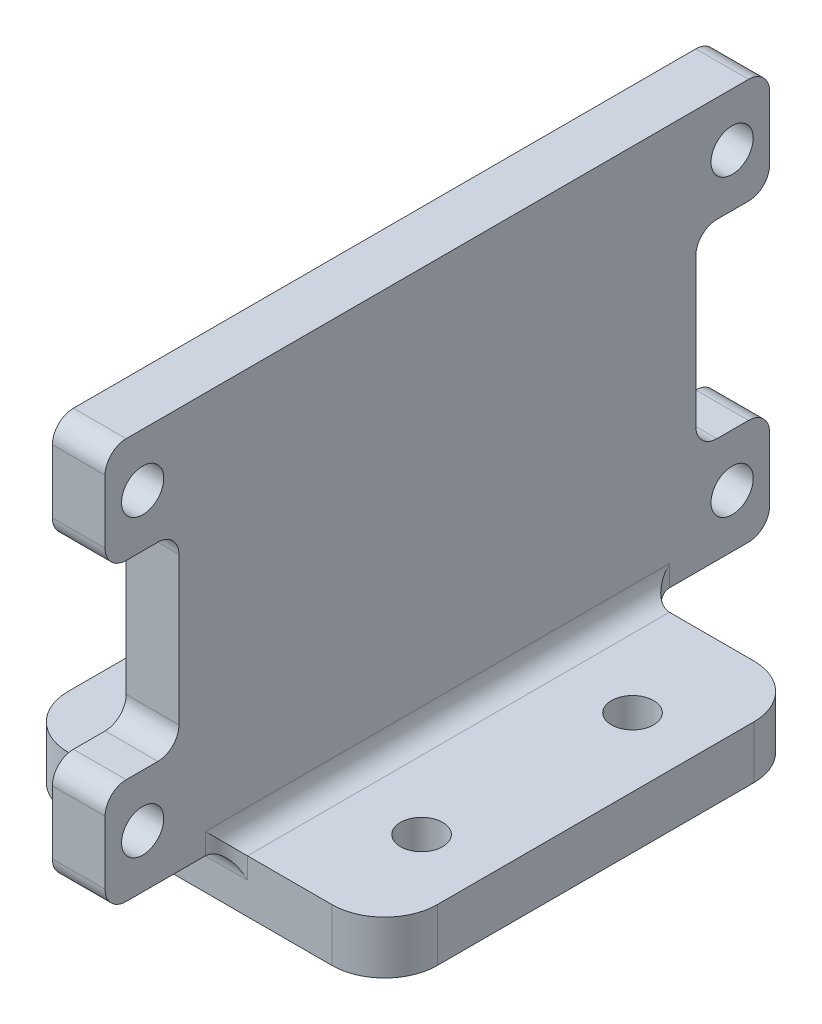
SolidWorks part; units mm, degrees
ref_plane "Plan de face" through (0, 0, 0) normal (0, 0, 1) x (1, 0, 0)
ref_plane "Plan de dessus" through (0, 0, 0) normal (0, 1, 0) x (1, 0, 0)
ref_plane "Plan de droite" through (0, 0, 0) normal (1, 0, 0) x (0, 0, -1)
sketch "Esquisse2" plane through (0, 0, 0) normal (0, 1, 0) x (1, 0, 0)
  line L1 (-17.5, -20) -> (17.5, -20)
  line L2 (-17.5, -20) -> (-17.5, 20)
  line L3 (-17.5, 20) -> (17.5, 20)
  line L4 (17.5, -20) -> (17.5, 20)
  line L5 (-17.5, -20) -> (17.5, 20) construction
  line L6 (-17.5, 20) -> (17.5, -20) construction
  point P0 (0, 0)
  dimension "D1" = 35
  dimension "D2" = 40
extrude "Boss.-Extru.1" add sketch "Esquisse2" along normal blind 5
sketch "Esquisse3" plane through (0, 0, 0) normal (1, 0, 0) x (0, 0, -1)
  line L1 (-31.5, 5) -> (31.5, 5)
  line L2 (-31.5, 5) -> (-31.5, 43)
  line L3 (-31.5, 43) -> (31.5, 43)
  line L4 (31.5, 5) -> (31.5, 43)
  line L5 (0, 5) -> (0, 0) construction
  line L6 (-20, 5) -> (20, 5) construction
  dimension "D1" = 38
  dimension "D2" = 63
extrude "Boss.-Extru.2" add sketch "Esquisse3" along normal mid plane 5
sketch "Esquisse4" plane through (2.5, 0, 0) normal (1, 0, 0) x (0, 0, -1)
  line L0 (-27.94, 37.97) -> (-27.94, 10.03) construction
  line L1 (-27.94, 10.03) -> (27.94, 10.03) construction
  line L2 (27.94, 10.03) -> (27.94, 37.97) construction
  line L3 (27.94, 37.97) -> (-27.94, 37.97) construction
  line L4 (0, 10.03) -> (0, 0) construction
  line L5 (-27.94, 24) -> (-31.5, 24) construction
  line L6 (-31.5, 43) -> (-31.5, 5) construction
  circle A0 centre (-27.94, 37.97) radius 2
  circle A1 centre (-27.94, 10.03) radius 2
  circle A2 centre (27.94, 37.97) radius 2
  circle A3 centre (27.94, 10.03) radius 2
  dimension "D1" = 4
  dimension "D2" = 4
  dimension "D3" = 4
  dimension "D4" = 55.88
  dimension "D5" = 27.94
extrude "Enlèv. mat.-Extru.1" cut sketch "Esquisse4" against normal up to next
sketch "Esquisse5" plane through (2.5, 0, 0) normal (1, 0, 0) x (0, 0, -1)
  line L0 (-31.5, 43) -> (-31.5, 5) construction
  line L1 (-31.5, 33) -> (-24.5, 33)
  line L2 (-31.5, 33) -> (-31.5, 15)
  line L3 (-31.5, 15) -> (-24.5, 15)
  line L4 (-24.5, 33) -> (-24.5, 15)
  line L5 (-31.5, 24) -> (-24.5, 24) construction
  line L7 (0, 0) -> (0, 16.9686) construction
  line L8 (-20, 0) -> (20, 0) construction
  line L9 (31.5, 15) -> (24.5, 15)
  line L10 (24.5, 33) -> (24.5, 15)
  line L11 (31.5, 33) -> (24.5, 33)
  line L12 (31.5, 33) -> (31.5, 15)
  dimension "D1" = 7
  dimension "D2" = 18
extrude "Enlèv. mat.-Extru.2" cut sketch "Esquisse5" against normal up to next
fillet "Congé1" radius 2 14 edges at (0, 5, -31.5) (0, 15, -24.5) (0, 15, -31.5) (0, 33, -24.5) (0, 43, -31.5) (0, 33, -31.5) (0, 15, 24.5) (0, 5, 31.5) (0, 15, 31.5) (0, 33, 24.5) (0, 33, 31.5) (0, 43, 31.5) (-2.5, 5, 0) (2.5, 5, 0)
fillet "Congé2" radius 5 4 edges at (-17.5, 2.5, 20) (-17.5, 2.5, -20) (17.5, 2.5, 20) (17.5, 2.5, -20)
fillet "Congé3" radius 2 6 edges at (-2.5, 6, 20) (2.5, 6, 20) (0, 5, 20) (2.5, 6, -20) (-2.5, 6, -20) (0, 5, -20)
sketch "Esquisse6" plane through (0, 5, 0) normal (0, 1, 0) x (1, 0, 0)
  line L0 (-11, 10) -> (-11, -10) construction
  line L1 (-11, 0) -> (0, 0) construction
  line L3 (0, 0) -> (0, -7.5172) construction
  circle A0 centre (-11, 10) radius 2
  circle A1 centre (-11, -10) radius 2
  circle A2 centre (11, -10) radius 2
  circle A3 centre (11, 10) radius 2
  dimension "D2" = 4
  dimension "D1" = 20
  dimension "D3" = 11
extrude "Enlèv. mat.-Extru.3" cut sketch "Esquisse6" against normal up to next
